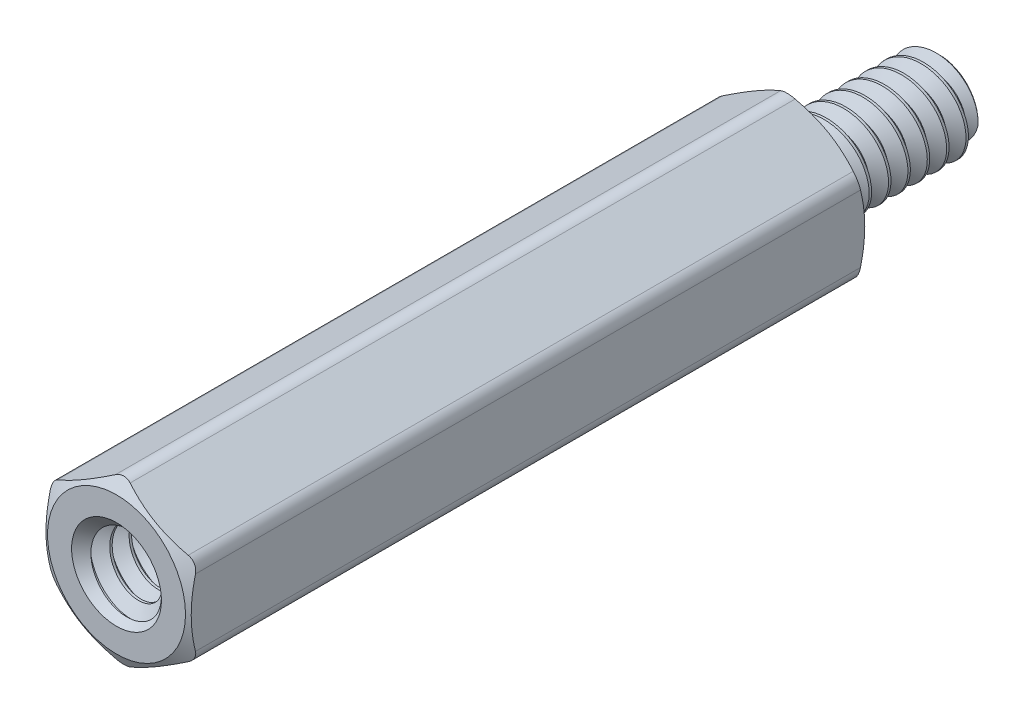
SolidWorks part; units mm, degrees
ref_plane "Front Plane" through (0, 0, 0) normal (0, 0, 1) x (1, 0, 0)
ref_plane "Top Plane" through (0, 0, 0) normal (0, 1, 0) x (1, 0, 0)
ref_plane "Right Plane" through (0, 0, 0) normal (1, 0, 0) x (0, 0, -1)
sketch "Sketch1" plane through (0, 0, 0) normal (0, 0, 1) x (1, 0, 0)
  line L1 (2.3813, 1.3748) -> (0, 2.7496)
  line L2 (0, 2.7496) -> (-2.3812, 1.3748)
  line L3 (-2.3812, 1.3748) -> (-2.3812, -1.3748)
  line L4 (-2.3812, -1.3748) -> (0, -2.7496)
  line L5 (0, -2.7496) -> (2.3813, -1.3748)
  line L6 (2.3813, -1.3748) -> (2.3813, 1.3748)
  circle A0 centre (0, 0) radius 2.3812 construction
  point P10 (0, -2.3812)
  dimension "Hex Size" = 4.7625
sketch "Sketch2" plane through (0, 0, 0) normal (1, 0, 0) x (0, 0, -1)
  line L0 (4.7625, 0) -> (-22.225, 0) construction
  line L2 (0, 1.4224) -> (0, -1.4224) construction
  line L3 (-15.875, 1.4224) -> (-15.875, -1.4224) construction
  line L4 (-22.8203, 1.4911) -> (-22.5028, 0.9412) construction
  line L5 (-22.5028, 0.9412) -> (-22.1853, 1.4911) construction
  line L6 (-22.1853, 1.4911) -> (-22.8203, 1.4911) construction
  line L7 (-22.7806, 1.4224) -> (-22.225, 1.4224) construction
  line L8 (-22.5425, 1.01) -> (-22.4631, 1.01) construction
  line L9 (-22.5028, 1.01) -> (-22.5028, 0.9412) construction
  line L10 (-22.5028, 1.4224) -> (-22.5028, 1.4911) construction
  line L11 (4.7228, 1.4911) -> (5.3578, 1.4911) construction
  line L12 (5.3578, 1.4911) -> (5.0403, 0.9412) construction
  line L13 (5.0403, 0.9412) -> (4.7228, 1.4911) construction
  line L14 (4.7625, 1.4224) -> (5.3181, 1.4224) construction
  line L15 (5.0006, 1.01) -> (5.08, 1.01) construction
  line L16 (5.0403, 1.01) -> (5.0403, 0.9412) construction
  line L17 (5.0403, 1.4224) -> (5.0403, 1.4911) construction
  line L18 (0, 2.7496) -> (-22.225, 2.7496) construction
  point P6 (0, 0)
  point P9 (-15.875, 0)
  dimension "Length" = 22.225
sketch "Sketch3" plane through (0, 0, 0) normal (1, 0, 0) x (0, 0, -1)
  line L0 (-15.875, 0) -> (4.7625, 0)
  line L1 (-15.875, 1.4224) -> (-15.875, -1.4224) construction
  line L2 (4.7625, 0) -> (4.7625, 1.2637)
  line L3 (4.7625, 1.2637) -> (4.6038, 1.4224)
  line L4 (4.6038, 1.4224) -> (0.8096, 1.4224)
  line L5 (0.8096, 1.4224) -> (0.5715, 1.01)
  line L6 (-15.875, 0) -> (-15.875, 1.2636)
  line L7 (-15.875, 1.2636) -> (-16.0337, 1.4224)
  line L8 (-16.0337, 1.4224) -> (-22.0663, 1.4224)
  line L9 (-22.0663, 1.4224) -> (-22.225, 1.5811)
  line L10 (4.6038, 0) -> (4.6038, -1.4224) construction
  line L11 (-22.225, 1.5811) -> (-22.225, 2.3812)
  line L12 (-22.225, 2.3812) -> (0, 2.3812)
  line L14 (0.5715, 1.01) -> (0.1587, 1.01)
  line L15 (0, 1.1687) -> (0, 2.3812)
  arc A0 (0, 1.1687) -> (0.1587, 1.01) centre (0.1587, 1.1687) ccw
  point P5 (-22.225, -2.3812)
  point P8 (-20.6375, -1.4224)
  point P9 (3.175, -1.4224)
  point P27 (0, 1.01)
  dimension "D4" = 0.1588
  dimension "D2" = 0.1588
  dimension "D1" = 45
  dimension "D6" = 1.5875
  dimension "D7" = 60
  dimension "D3" = 1.5875
  dimension "D5" = 0.5715
revolve "Revolve1" add sketch "Sketch3" angle 360 about L0 region at (0, 1.2118, 7.9406)
sketch "Sketch4" plane through (0, 0, 22.225) normal (0, 0, 1) x (1, 0, 0)
  line L0 (0, 2.3812) -> (0, 1.4224) construction
  line L1 (-2.3812, 1.3748) -> (-2.3812, -1.3748)
  line L2 (-2.3812, -1.3748) -> (0, -2.7496)
  line L3 (0, -2.7496) -> (2.3812, -1.3748)
  line L4 (2.3812, -1.3748) -> (2.3812, 1.3748)
  line L5 (2.3812, 1.3748) -> (0, 2.7496)
  line L6 (0, 2.7496) -> (-2.3812, 1.3748)
  circle A0 centre (0, 0) radius 2.3812 construction
  circle A1 centre (0, 0) radius 1.9018
  circle A2 centre (0, 0) radius 2.3812 construction
  point P16 (0, 1.9018)
extrude "Boss-Extrude1" add sketch "Sketch4" against normal up to surface (22.225 mm away) up to face at (0, 2.3812, 0)
sketch "Sketch5" plane through (0, 0, 22.225) normal (0, 0, 1) x (1, 0, 0)
  line L0 (-0.8159, 1.1652) -> (0.8159, -1.1652) construction
  line L1 (0, 1.4224) -> (0, -1.4224) construction
  line L3 (0, -2.9435) -> (0, 2.9435) construction
  circle A0 centre (0, 0) radius 2.2622
  point P11 (0.8159, -1.1652)
  dimension "D1" = 4.5244
  dimension "D2" = 35
extrude "Cut-Extrude1" cut sketch "Sketch5" against normal through all draft 60 flip side to cut
sketch "Sketch6" plane through (0, 0, 0) normal (0, 0, -1) x (-1, 0, 0)
  circle A0 centre (0, 0) radius 2.2622
  circle A1 centre (0, 0) radius 2.2622 construction
extrude "Cut-Extrude2" cut sketch "Sketch6" against normal through all draft 60 flip side to cut
fillet "Fillet1" radius 0.4763 6 edges at (0, 2.7496, 11.1125) (-2.3812, -1.3748, 11.1125) (0, -2.7496, 11.1125) (2.3812, -1.3748, 11.1125) (2.3812, 1.3748, 11.1125) (-2.3812, 1.3748, 11.1125)
sketch "Drawing1" plane through (0, 0, 0) normal (1, 0, 0) x (0, 0, -1)
  line L0 (-22.225, 1.4224) -> (-15.875, 1.4224) construction
  line L1 (-15.875, 1.4224) -> (-15.875, -1.4224) construction
  line L2 (-15.875, -1.4224) -> (-22.225, -1.4224) construction
sketch "Sketch7" plane through (0, 0, 0) normal (-1, 0, 0) x (0, 0, 1)
  line L0 (-5.0006, 1.01) -> (-5.08, 1.01)
  line L1 (-5.08, 1.01) -> (-5.338, 1.4568)
  line L2 (-5.3578, 1.4911) -> (-5.0403, 0.9412) construction
  line L3 (-5.338, 1.4568) -> (-4.7427, 1.4568)
  line L4 (-5.0403, 0.9412) -> (-4.7228, 1.4911) construction
  line L5 (-4.7427, 1.4568) -> (-5.0006, 1.01)
  line L6 (-5.0403, 1.4224) -> (-5.0403, 1.4911) construction
  point P12 (-5.0403, 1.4568)
sketch "Sketch8" plane through (0, 0, -4.7625) normal (0, 0, -1) x (-1, 0, 0)
  circle A0 centre (0, 0) radius 1.4224
curve "Helix/Spiral1" pitch 0.635 height 4.6196 radius 1.4224 centre (0, 0, -4.7625) axis (0, 0, 1) start towards (0, 1, 0)
sweep "Cut-Sweep1" cut profiles "Sketch7" path "Helix/Spiral1" align with end faces yes
sketch "Sketch9" plane through (0, 0, 15.875) normal (0, 0, 1) x (1, 0, 0)
  circle A0 centre (0, 0) radius 1.5811
extrude "Boss-Extrude2" add sketch "Sketch9" along normal up to surface (6.35 mm away) up to face at (0, 1.5811, 22.225)
sketch "Sketch10" plane through (0, 0, 0) normal (1, 0, 0) x (0, 0, -1)
  line L0 (4.7625, 0) -> (-22.225, 0) construction
  line L1 (-15.875, 1.4224) -> (-22.225, 1.4224)
  line L2 (-15.875, 1.4224) -> (-15.875, 0)
  line L3 (-15.875, 0) -> (-22.225, 0)
  line L4 (-22.225, 1.4224) -> (-22.225, 0)
revolve "Revolve2" add sketch "Sketch10" angle 360 about L0
sketch "Sketch11" plane through (0, 0, 22.225) normal (0, 0, 1) x (1, 0, 0)
  circle A0 centre (0, 0) radius 1.4224
  circle A1 centre (0, 0) radius 1.4224 construction
sketch "Sketch12" plane through (0, 0, 0) normal (1, 0, 0) x (0, 0, -1)
  line L0 (-22.5425, 1.01) -> (-22.4631, 1.01)
  line L1 (-22.4631, 1.01) -> (-22.2052, 1.4568)
  line L2 (-22.5028, 0.9412) -> (-22.1853, 1.4911) construction
  line L3 (-22.2052, 1.4568) -> (-22.8005, 1.4568)
  line L4 (-22.8203, 1.4911) -> (-22.5028, 0.9412) construction
  line L5 (-22.8005, 1.4568) -> (-22.5425, 1.01)
  line L6 (-22.5028, 1.4224) -> (-22.5028, 1.4911) construction
  point P12 (-22.5028, 1.4568)
curve "Helix/Spiral2" pitch 0.635 height 6.985 radius 1.4224 centre (0, 0, 22.225) axis (0, 0, -1) start towards (0, 1, 0)
sweep "Cut-Sweep2" cut profiles "Sketch12" path "Helix/Spiral2" align with end faces yes
combine bodies "Combine1" operation type subtract main body 113 bodies to subtract 114
sketch "Sketch13" plane through (0, 0, 22.225) normal (0, 0, 1) x (1, 0, 0)
  circle A0 centre (0, 0) radius 1.4732
  dimension "D1" = 0.0508
extrude "Cut-Extrude3" cut sketch "Sketch13" against normal through all draft 45
equation "\"Thread Pitch (B)/8@Sketch2\"=\"Thread Pitch (B)@Sketch2\"/8"
equation "\"Thread Pitch (A)/8@Sketch2\"=\"Thread Pitch (A)@Sketch2\"/8"
equation "\"D1@Sketch5\" = \"Hex Size@Sketch1\" * .95"
equation "\"D1@Fillet1\" = \"Hex Size@Sketch1\" * .1"
equation "\"D2@Sketch3\" = \"Thread Pitch (A)@Sketch2\" * .25"
equation "\"D4@Sketch3\" = \"D2@Sketch3\""
equation "\"D6@Sketch3\" = \"Thread Pitch (A)@Sketch2\" * 2.5"
equation "\"D3@Helix/Spiral1\" = \"Thread Length (A)@Sketch2\" - \"D5@Sketch3\" * .25"
equation "\"D4@Helix/Spiral1\" = \"Thread Pitch (A)@Sketch2\""
equation "\"D3@Sketch3\" = \"Thread Pitch (B)@Sketch2\" * 2.5"
equation "\"D5@Sketch3\" = \"Thread Length (A)@Sketch2\" * .12"
equation "\"D3@Helix/Spiral2\" = \"Minimum Thread Length (B)@Sketch2\" + \"Thread Pitch (B)@Sketch2\""
equation "\"D4@Helix/Spiral2\" = \"Thread Pitch (B)@Sketch2\""
